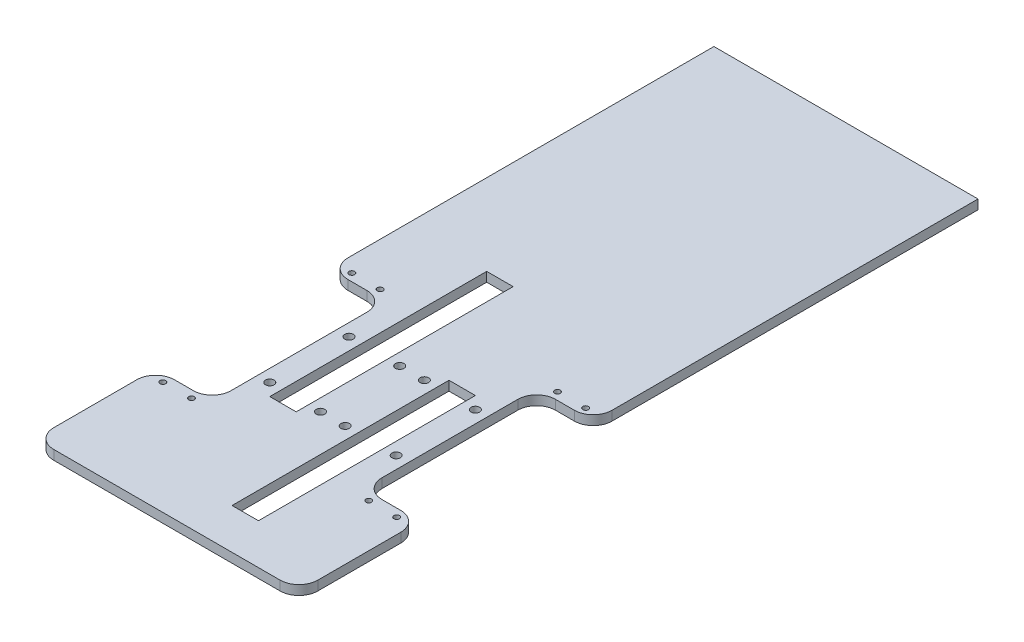
SolidWorks part; units mm, degrees
ref_plane "Front Plane" through (0, 0, 0) normal (0, 0, 1) x (1, 0, 0)
ref_plane "Top Plane" through (0, 0, 0) normal (0, 1, 0) x (1, 0, 0)
ref_plane "Right Plane" through (0, 0, 0) normal (1, 0, 0) x (0, 0, -1)
sketch "Sketch1" plane through (0, 0, 0) normal (0, 1, 0) x (1, 0, 0)
  line L1 (-70, -170) -> (70, -170)
  line L2 (-70, -170) -> (-70, 170)
  line L3 (-70, 170) -> (70, 170)
  line L4 (70, -170) -> (70, 170)
  line L5 (-70, -170) -> (70, 170) construction
  line L6 (-70, 170) -> (70, -170) construction
  point P0 (0, 0)
  dimension "D1" = 140
  dimension "D2" = 340
extrude "Boss-Extrude1" add sketch "Sketch1" along normal blind 5
sketch "Sketch3" plane through (0, 5, 0) normal (0, 1, 0) x (1, 0, 0)
  line L0 (0, 170) -> (0, -170) construction
  line L1 (70, 170) -> (-70, 170) construction
  line L2 (-70, -170) -> (70, -170) construction
  line L3 (-70, -120) -> (70, -120)
  line L4 (-70, 170) -> (-70, -170) construction
  line L5 (70, -170) -> (70, 170) construction
  line L6 (-70, -40) -> (70, -40)
  line L7 (-40, -40) -> (-40, -120)
  line L8 (40, -40) -> (40, -120)
  line L9 (-70, -40) -> (-70, -121.1832)
  line L10 (70, -40) -> (70, -120)
  line M1 (70, -170) -> (70, 170)
  line M3 (-70, 170) -> (-70, -170)
  dimension "D1" = 50
  dimension "D2" = 80
  dimension "D3" = 30
  dimension "D4" = 30
extrude "Cut-Extrude1" cut sketch "Sketch3" against normal through all contours L7 L6 L3 M3 | L6 L8 L3 M1 region at (-55, 5, 80) region at (55, 5, 80)
sketch "Sketch5" plane through (0, 0, 0) normal (0, -1, 0) x (-1, 0, 0)
  line L0 (-40, -108.473) -> (40.1724, -108.473)
  line L1 (-40, -40) -> (-40, -120) construction
sketch "Sketch6" plane through (0, 0, 0) normal (0, -1, 0) x (-1, 0, 0)
  line L0 (-40, -40) -> (-40, -120) construction
  line L1 (0.0862, -108.473) -> (0.0862, -54.3323) construction
  line L2 (-40, -108.473) -> (40.1724, -108.473) construction
  line L3 (-12.9462, -108.473) -> (13.1186, -108.473)
  line L4 (-12.9462, -108.473) -> (-12.9462, -101.973)
  line L5 (13.1186, -108.473) -> (13.1186, -101.973)
  circle A0 centre (-33.5, -101.973) radius 2.25
  circle A1 centre (-33.5, -59.973) radius 2.25
  circle A2 centre (33.5, -101.973) radius 2.25
  circle A3 centre (33.5, -59.973) radius 2.25
  circle A4 centre (6.6186, -101.973) radius 2.25
  circle A5 centre (-6.4462, -101.973) radius 2.25
  circle A6 centre (6.6186, -59.973) radius 2.25
  circle A7 centre (-6.4462, -59.973) radius 2.25
  point P20 (0.0862, -108.473)
  dimension "D1" = 6.5
extrude "Cut-Extrude2" cut sketch "Sketch6" against normal through all contours A1 | A0 | A7 | A5 | A4 | A6 | A3 | A2 region at (33.5, 0, 101.973) region at (33.5, 0, 59.973) region at (-33.5, 0, 101.973) region at (-33.5, 0, 59.973) region at (-6.6186, 0, 101.973) region at (6.4462, 0, 101.973) region at (-6.6186, 0, 59.973) region at (6.4462, 0, 59.973)
sketch "Sketch7" plane through (0, 0, 0) normal (0, -1, 0) x (-1, 0, 0)
  line L0 (-40, -108.473) -> (40.1724, -108.473) construction
  line L1 (-12.9462, -108.473) -> (-27, -108.473)
  line L2 (-12.9462, -108.473) -> (-12.9462, -53.473)
  line L3 (-12.9462, -53.473) -> (-27, -53.473)
  line L4 (-27, -108.473) -> (-27, -53.473)
  line L5 (-12.9462, -94.973) -> (-12.9462, -108.473) construction
  line L6 (27, -108.473) -> (27, -89.973) construction
  line L7 (27, -108.473) -> (13.1186, -108.473)
  line L8 (27, -108.473) -> (27, -53.473)
  line L9 (27, -53.473) -> (13.1186, -53.473)
  line L10 (13.1186, -108.473) -> (13.1186, -53.473)
  dimension "D1" = 55
sketch "Sketch8" plane through (0, 0, 0) normal (0, -1, 0) x (1, 0, 0)
  line L0 (12.9462, 53.473) -> (27, 53.473) construction
  line L1 (27, 108.473) -> (27, 53.473) construction
  line L2 (12.9462, 108.473) -> (12.9462, 53.473) construction
  line L3 (-27, 53.473) -> (-13.1186, 53.473) construction
  line L4 (-13.1186, 108.473) -> (-13.1186, 53.473) construction
  line L5 (-27, 108.473) -> (-27, 53.473) construction
  line L6 (12.9462, 53.473) -> (27, 53.473)
  line L7 (27, 108.473) -> (27, 53.473)
  line L8 (12.9462, 108.473) -> (12.9462, 53.473)
  line L9 (-27, 53.473) -> (-13.1186, 53.473)
  line L10 (-13.1186, 108.473) -> (-13.1186, 53.473)
  line L11 (-27, 108.473) -> (-27, 53.473)
  line L12 (-27, 108.473) -> (-13.1186, 108.473)
  line L13 (12.9462, 108.473) -> (27, 108.473)
sketch "Sketch9" plane through (0, 0, 0) normal (0, -1, 0) x (1, 0, 0)
  line L0 (-27, 108.473) -> (-27, 53.473)
  line L1 (40, 108.473) -> (-40.1724, 108.473) construction
  line L2 (-27, 53.473) -> (-13, 53.473)
  line L3 (-13, 53.473) -> (-13, 108.473)
  line L4 (-13, 108.473) -> (-27, 108.473)
  line L5 (13, 108.473) -> (13, 53.473)
  line L6 (13, 53.473) -> (27, 53.473)
  line L7 (27, 53.473) -> (27, 108.473)
  line L8 (27, 108.473) -> (13, 108.473)
  line L9 (-40, 40) -> (-40, 120) construction
  line L10 (40, 40) -> (40, 120) construction
  dimension "D1" = 14
  dimension "D2" = 13
  dimension "D3" = 13
  dimension "D4" = 14
  dimension "D5" = 55
  dimension "D6" = 55
extrude "Cut-Extrude3" cut sketch "Sketch9" against normal through all
sketch "Sketch10" plane through (0, 5, 0) normal (0, 1, 0) x (1, 0, 0)
  line L1 (13, -108.473) -> (27, -108.473)
  line L2 (13, -108.473) -> (13, -168.473)
  line L3 (13, -168.473) -> (27, -168.473)
  line L4 (27, -108.473) -> (27, -168.473)
  line L6 (-13, -53.473) -> (-27, -53.473)
  line L7 (-13, -53.473) -> (-13, 6.527)
  line L8 (-13, 6.527) -> (-27, 6.527)
  line L9 (-27, -53.473) -> (-27, 6.527)
  dimension "D1" = 14
  dimension "D2" = 60
  dimension "D3" = 14
  dimension "D4" = 60
extrude "Cut-Extrude4" cut sketch "Sketch10" against normal through all
sketch "Sketch12" plane through (0, 0, 0) normal (0, 1, 0) x (1, 0, 0)
  line L1 (-70, -170) -> (70, -170)
  line L2 (-70, -170) -> (-70, -190)
  line L3 (-70, -190) -> (70, -190)
  line L4 (70, -170) -> (70, -190)
  dimension "D1" = 20
  dimension "D2" = 140
extrude "Boss-Extrude2" add sketch "Sketch12" along normal blind 5
sketch "Sketch13" plane through (0, 5, 0) normal (0, 1, 0) x (1, 0, 0)
  circle A0 centre (33.5, -101.973) radius 3.5
  circle A1 centre (6.4462, -101.973) radius 3.5
  circle A2 centre (-6.6186, -101.973) radius 3.5
  circle A3 centre (-33.5, -101.973) radius 3.5
  circle A4 centre (-33.5, -59.973) radius 3.5
  circle A5 centre (-6.6186, -59.973) radius 3.5
  circle A6 centre (6.4462, -59.973) radius 3.5
  circle A7 centre (33.5, -59.973) radius 3.5
  dimension "D1" = 7
  dimension "D2" = 7
  dimension "D3" = 7
  dimension "D4" = 7
  dimension "D5" = 7
  dimension "D6" = 7
  dimension "D7" = 7
  dimension "D8" = 7
extrude "Cut-Extrude5" [suppressed] cut sketch "Sketch13" against normal blind 3.6
sketch "Sketch14" plane through (0, 5, 0) normal (0, 1, 0) x (1, 0, 0)
  line L0 (-70, -30) -> (70, -30)
  line L1 (-70, 170) -> (-70, -40) construction
  line L2 (70, -40) -> (70, 170) construction
  line L3 (-70, -130) -> (70, -130)
  line L4 (-70, -120) -> (-70, -190) construction
  line L5 (70, -190) -> (70, -120) construction
  line L6 (-70, -40) -> (-40, -40) construction
  line L7 (-70, -120) -> (-40, -120) construction
  line L8 (0, -2.75) -> (0, 2.75) construction
  circle A0 centre (-62, -30) radius 1.5
  circle A1 centre (-47, -30) radius 1.5
  circle A2 centre (47, -30) radius 1.5
  circle A3 centre (62, -30) radius 1.5
  circle A4 centre (-62, -130.17) radius 1.5
  circle A5 centre (-47, -130) radius 1.5
  circle A6 centre (47, -130) radius 1.5
  circle A7 centre (62, -130.17) radius 1.5
  dimension "D3" = 3
  dimension "D4" = 8
  dimension "D5" = 15
  dimension "D6" = 8
  dimension "D7" = 15
  dimension "D1" = 10
  dimension "D2" = 10
extrude "Cut-Extrude6" cut sketch "Sketch14" against normal through all contours A0 | A1 | A2 | A3 | A4 | A5 | A6 | A7
sketch "Sketch15" plane through (0, 5, 0) normal (0, 1, 0) x (1, 0, 0)
  line L0 (0, -2.75) -> (0, 2.75) construction
  line L1 (-70, -40) -> (-40, -40)
  line L2 (-70, -40) -> (-70, -34)
  line L3 (-70, -34) -> (-40, -34)
  line L4 (-40, -40) -> (-40, -34)
  line L5 (-70, -120) -> (-40, -120)
  line L6 (-70, -120) -> (-70, -126)
  line L7 (-70, -126) -> (-40, -126)
  line L8 (-40, -120) -> (-40, -126)
  line L9 (70, -34) -> (40, -34)
  line L10 (40, -40) -> (40, -34)
  line L11 (70, -40) -> (40, -40)
  line L12 (70, -40) -> (70, -34)
  line L13 (70, -126) -> (40, -126)
  line L14 (40, -120) -> (40, -126)
  line L15 (70, -120) -> (40, -120)
  line L16 (70, -120) -> (70, -126)
  dimension "D1" = 6
  dimension "D2" = 30
  dimension "D3" = 30
  dimension "D4" = 6
extrude "Cut-Extrude7" cut sketch "Sketch15" against normal through all
fillet "Fillet1" radius 10 6 edges at (70, 2.5, 126) (70, 2.5, 34) (-70, 2.5, 126) (-70, 2.5, 34) (-70, 2.5, 190) (70, 2.5, 190)
fillet "Fillet2" radius 10 4 edges at (40, 2.5, 126) (40, 2.5, 34) (-40, 2.5, 126) (-40, 2.5, 34)
